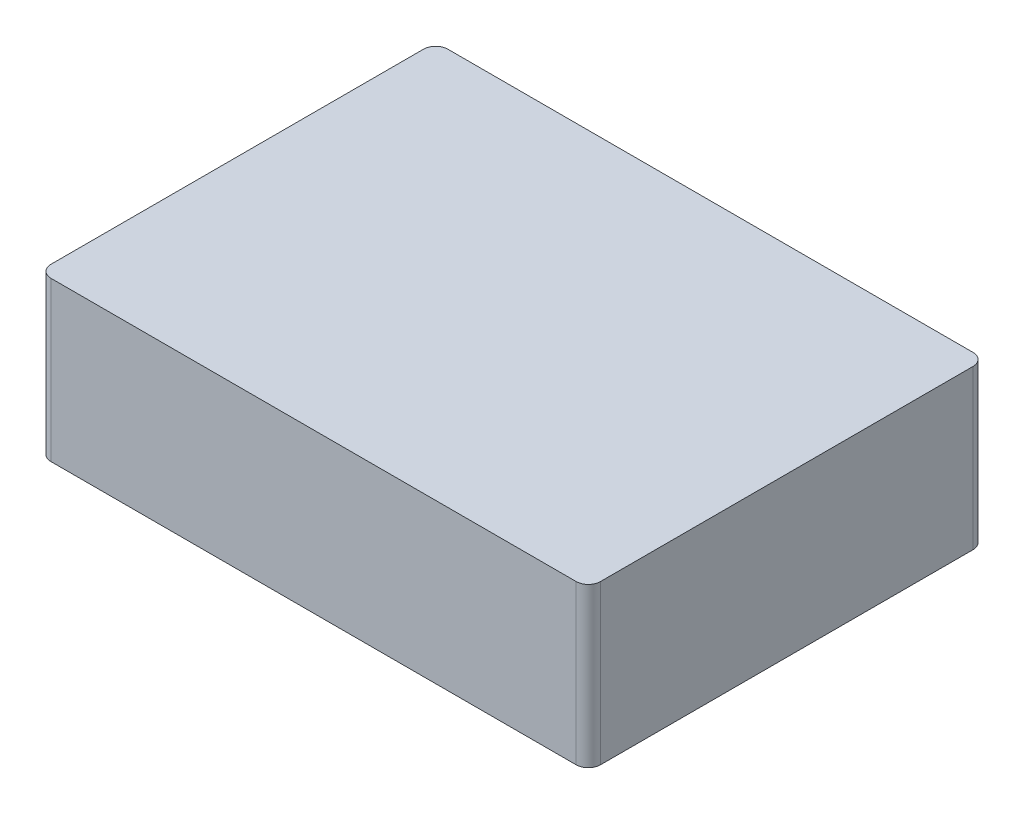
SolidWorks part; units mm, degrees
material "ABS"
ref_plane "Front Plane" through (0, 0, 0) normal (0, 0, 1) x (1, 0, 0)
ref_plane "Top Plane" through (0, 0, 0) normal (0, 1, 0) x (1, 0, 0)
ref_plane "Right Plane" through (0, 0, 0) normal (1, 0, 0) x (0, 0, -1)
sketch "Sketch1" plane through (0, 0, 0) normal (0, 1, 0) x (1, 0, 0)
  line L1 (-45, -32.5) -> (45, -32.5)
  line L2 (-45, -32.5) -> (-45, 32.5)
  line L3 (-45, 32.5) -> (45, 32.5)
  line L4 (45, -32.5) -> (45, 32.5)
  line L5 (-45, -32.5) -> (45, 32.5) construction
  line L6 (-45, 32.5) -> (45, -32.5) construction
  point P0 (0, 0)
  dimension "D1" = 90
  dimension "D2" = 65
extrude "Boss-Extrude1" add sketch "Sketch1" along normal blind 26
fillet "Fillet1" radius 2 4 edges at (-45, 13, 32.5) (-45, 13, -32.5) (45, 13, -32.5) (45, 13, 32.5)
